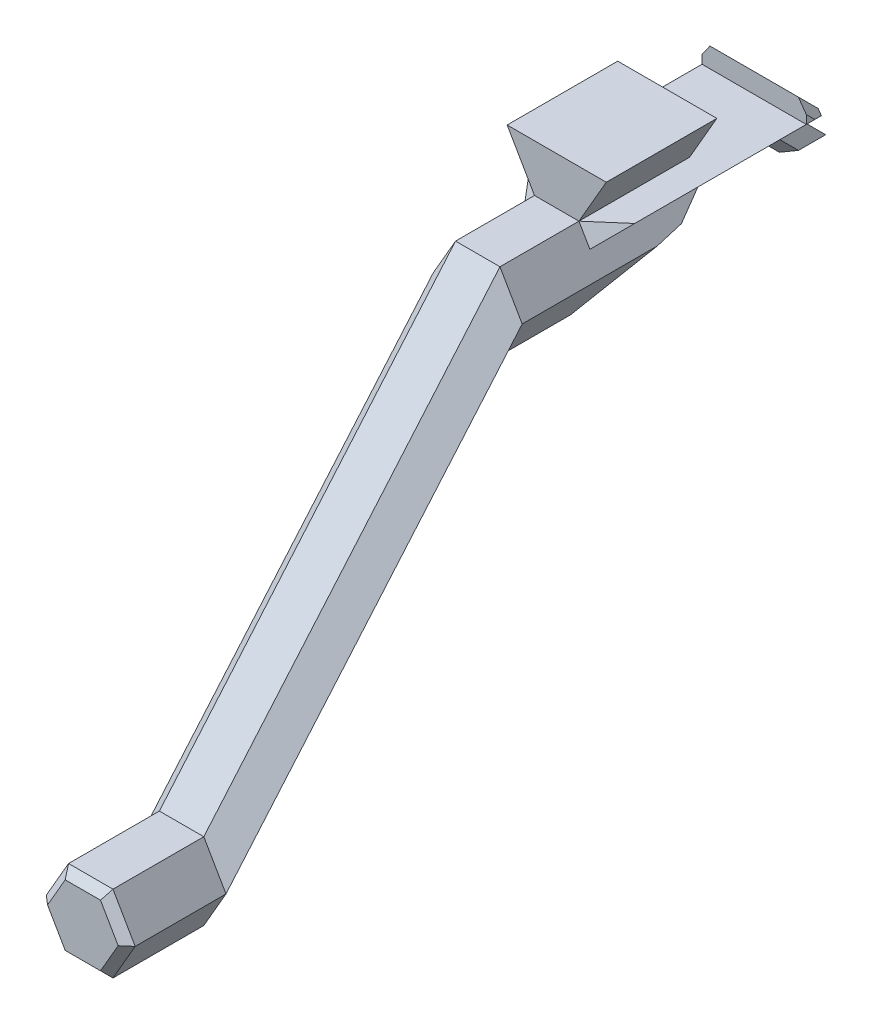
SolidWorks part; units mm, degrees
ref_plane "Front Plane" through (0, 0, 0) normal (0, 0, 1) x (1, 0, 0)
ref_plane "Top Plane" through (0, 0, 0) normal (0, 1, 0) x (1, 0, 0)
ref_plane "Right Plane" through (0, 0, 0) normal (1, 0, 0) x (0, 0, -1)
sketch "Sketch1" plane through (0, 0, 0) normal (0, 0, 1) x (1, 0, 0)
  line L1 (5.715, 0) -> (2.8575, 4.9493)
  line L2 (2.8575, 4.9493) -> (-2.8575, 4.9493)
  line L3 (-2.8575, 4.9493) -> (-5.715, 0)
  line L4 (-5.715, 0) -> (-2.8575, -4.9493)
  line L5 (-2.8575, -4.9493) -> (2.8575, -4.9493)
  line L6 (2.8575, -4.9493) -> (5.715, 0)
  circle A0 centre (0, 0) radius 4.9493 construction
  dimension "D1" = 11.43
extrude "Boss-Extrude1" add sketch "Sketch1" along normal blind 25.4
ref_plane "Plane4" through (0, 0, 63.5) normal (0, 0, 1) x (1, 0, 0)
sketch "Sketch2" plane through (0, 0, 63.5) normal (0, 0, 1) x (1, 0, 0)
  line L0 (5.715, 0) -> (2.8575, 4.9493) construction
  line L1 (5.715, 0) -> (2.8575, 4.9493)
  line L12 (5.715, -44.45) -> (2.8575, -39.5007)
  line L13 (2.8575, -39.5007) -> (-2.8575, -39.5007)
  line L14 (-2.8575, -39.5007) -> (-5.715, -44.45)
  line L15 (-5.715, -44.45) -> (-2.8575, -49.3993)
  line L16 (-2.8575, -49.3993) -> (2.8575, -49.3993)
  line L17 (2.8575, -49.3993) -> (5.715, -44.45)
extrude "Boss-Extrude2" add sketch "Sketch2" along normal blind 12.7 separate body contours L16 L17 L12 L13 L14 L15 region at (0, -44.45, 63.5)
sketch "Sketch3" plane through (0, 0, 0) normal (1, 0, 0) x (0, 0, -1)
  line L0 (-63.5, -44.45) -> (-63.5, -39.5007) construction
  line L1 (-63.5, -44.45) -> (-63.5, -39.5007)
  line L2 (-25.4, 0) -> (-25.4, 4.9493) construction
  line L3 (-25.4, 0) -> (-25.4, 4.9493)
  line L4 (-25.4, 4.9493) -> (-63.5, -39.5007)
loft "Loft1" add section face at (0, 0, 25.4) section face at (0, -44.45, 63.5) connector at (2.8575, -4.9493, 25.4) connector at (2.8575, -49.3993, 63.5)
sketch "Sketch4" plane through (0, 0, 0) normal (0, 0, -1) x (-1, 0, 0)
  line L0 (2.8575, 4.9493) -> (6.377, 11.0453)
  line L1 (6.377, 11.0453) -> (-6.377, 11.0453)
  line L2 (-6.377, 11.0453) -> (-2.8575, 4.9493)
  line L3 (-2.8575, 4.9493) -> (2.8575, 4.9493)
  dimension "D1" = 6.096
  dimension "D2" = 120
  dimension "D3" = 120
extrude "Boss-Extrude3" add sketch "Sketch4" against normal blind 15.24
chamfer "Chamfer1" distance 7.46 distance2 12.54 1 edges at (0, -4.9493, 0) first distance on face at (0, 2.7613, 0)
sketch "Sketch5" plane through (0, 0, 0) normal (0, 0, -1) x (-1, 0, 0)
  line L0 (-2.8575, 4.9493) -> (2.8575, 4.9493)
  line L1 (2.8575, 4.9493) -> (4.2655, 2.5107)
  line L2 (4.2655, 2.5107) -> (-4.2655, 2.5107)
  line L3 (-4.2655, 2.5107) -> (-2.8575, 4.9493)
extrude "Boss-Extrude4" add sketch "Sketch5" along normal blind 12.7
sketch "Sketch6" plane through (0, 0, -12.7) normal (0, 0, -1) x (-1, 0, 0)
  line L0 (-4.2655, 2.5107) -> (-6.7041, 4.9493)
  line L1 (-6.7041, 4.9493) -> (-2.8575, 4.9493)
  line L2 (-2.8575, 4.9493) -> (2.8575, 4.9493)
  line L3 (2.8575, 4.9493) -> (6.7041, 4.9493)
  line L4 (6.7041, 4.9493) -> (4.2655, 2.5107)
  line L5 (4.2655, 2.5107) -> (-4.2655, 2.5107)
  dimension "D1" = 135
extrude "Boss-Extrude5" add sketch "Sketch6" against normal blind 24.384
sketch "Sketch7" plane through (0, 0, 0) normal (1, 0, 0) x (0, 0, -1)
  line L0 (12.7, 4.9493) -> (10.16, 7.4893)
  line L1 (10.16, 7.4893) -> (10.16, 4.9493)
  line L2 (-11.684, 4.9493) -> (12.7, 4.9493) construction
  line L3 (10.16, 4.9493) -> (12.7, 4.9493)
  line L4 (12.7, 2.5107) -> (15.0944, 0.1162)
  line L5 (15.0944, 0.1162) -> (10.16, 0.1162)
  line L7 (12.7, 2.5107) -> (0, 2.5107) construction
  line L8 (10.16, 2.5107) -> (12.7, 2.5107)
  line L9 (10.16, 0.1162) -> (7.7656, 2.5107)
  line L10 (7.7656, 2.5107) -> (10.16, 2.5107)
  dimension "D1" = 2.54
  dimension "D2" = 45
  dimension "D3" = 45
  dimension "D4" = 4.9344
extrude "Boss-Extrude6" add sketch "Sketch7" along normal up to vertex (4.2655 mm away) and the other way up to vertex (4.2655 mm away) contours L10 L9 L5 L4 L8 region at (0, 1.3135, -11.43) up to point (4.2655, 2.5107, 0) other way up to point (-4.2655, 2.5107, 0)
extrude "Boss-Extrude7" add sketch "Sketch7<3>" along normal up to vertex (6.7041 mm away) and the other way up to vertex (6.7041 mm away) contours L1 L3 L0 region at (0, 5.796, -11.0067) up to point (6.7041, 4.9493, 11.684) other way up to point (-6.7041, 4.9493, 11.684)
sketch "Sketch7<3>" plane through (0, 0, 0) normal (1, 0, 0) x (0, 0, -1) same geometry as "Sketch7"
chamfer "Chamfer2" distance 3.556 angle 45 2 edges at (3.5615, 3.73, 11.684) (-3.5615, 3.73, 11.684)
chamfer "Chamfer3" distance 1.016 angle 45 17 edges at (-4.2655, 1.3135, -8.9628) (4.2655, 1.3135, -8.9628) (-4.6173, 7.9973, 0) (0, 11.0453, 0) (4.6173, 7.9973, 0) (-6.7041, 6.2193, -11.43) (6.7041, 6.2193, -11.43) (0, -49.3993, 76.2) (-4.2862, -46.9247, 76.2) (4.2863, -46.9247, 76.2) (-4.2863, -41.9753, 76.2) (4.2862, -41.9753, 76.2) (0, -39.5007, 76.2) (-4.2862, -2.4747, 8.3802) (-4.9902, 1.2553, 2.1102) (4.2863, -2.4747, 8.3802) (4.9902, 1.2553, 2.1102) first distance on face at (0, 1.3135, -8.9628) first distance on face at (4.2655, 1.3135, -11.43) first distance on face at (-4.6173, 7.9973, 7.62) first distance on face at (0, 11.0453, 7.62) first distance on face at (4.6173, 7.9973, 7.62) first distance on face at (0, 6.2193, -11.43) first distance on face at (-0.7144, -49.3993, 73.025) first distance on face at (-4.6434, -46.306, 73.025) first distance on face at (3.9291, -47.5433, 73.025) first distance on face at (-3.9291, -41.3567, 73.025) first distance on face at (4.6434, -42.594, 73.025) first distance on face at (0.7144, -39.5007, 73.025) first distance on face at (0, -0.8129, 5.5868)
